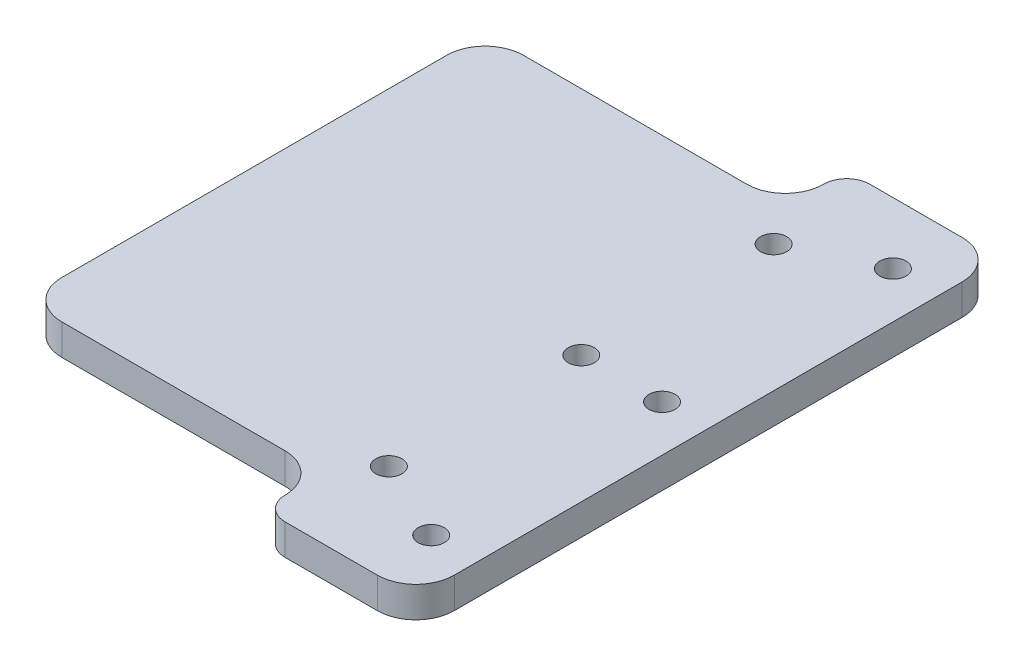
SolidWorks part; units mm, degrees
ref_plane "前视基准面" through (0, 0, 0) normal (0, 0, 1) x (1, 0, 0)
ref_plane "上视基准面" through (0, 0, 0) normal (0, 1, 0) x (1, 0, 0)
ref_plane "右视基准面" through (0, 0, 0) normal (1, 0, 0) x (0, 0, -1)
sketch "草图1" plane through (0, 0, 0) normal (0, 1, 0) x (1, 0, 0)
  line L0 (42.5, 25) -> (42.5, -25) construction
  line L5 (0, 0) -> (0, 30)
  line L6 (0, 30) -> (39, 30)
  line L7 (42.5, 0) -> (0, 0) construction
  line L8 (0, 0) -> (53, 0) construction
  line L9 (53, 30) -> (53, -30) construction
  line L10 (39, 30) -> (39, 38)
  line L11 (39, 38) -> (59, 38)
  line L12 (59, 38) -> (59, -38)
  line L13 (59, -38) -> (39, -38)
  line L14 (39, -38) -> (39, -30)
  line L15 (39, -30) -> (0, -30)
  line L16 (0, -30) -> (0, 0)
  circle A0 centre (42.5, 25) radius 1.7
  circle A1 centre (42.5, -25) radius 1.7
  circle A2 centre (42.5, 0) radius 1.7
  circle A3 centre (53, 30) radius 1.7
  circle A4 centre (53, 0) radius 1.7
  circle A5 centre (53, -30) radius 1.7
  point P0 (0, 0)
  dimension "D2" = 3.4
  dimension "D1" = 50
  dimension "D3" = 10.5
  dimension "D4" = 6
  dimension "D5" = 8
  dimension "D6" = 60
  dimension "D7" = 42.5
  dimension "D8" = 20
  dimension "D9" = 39
  dimension "D10" = 60
extrude "凸台-拉伸1" add sketch "草图1" along normal blind 4
sketch "草图2" plane through (0, 4, 0) normal (0, 1, 0) x (1, 0, 0)
  line L0 (-20.6269, -154.0352) -> (-20.6269, -168.0352) construction
  circle A1 centre (-20.6269, -168.0352) radius 1.5
  circle A2 centre (-20.6269, -168.0352) radius 1.5
  circle A3 centre (-17.1269, -171.5352) radius 1.5
  circle A4 centre (-17.1269, -171.5352) radius 1.5
  circle A5 centre (-10.1269, -164.5352) radius 1.5
  circle A6 centre (-10.1269, -164.5352) radius 1.5
  circle A7 centre (-10.1269, -178.5352) radius 1.5
  circle A8 centre (-10.1269, -178.5352) radius 1.5
  circle A9 centre (-3.1269, -171.5352) radius 1.5
  circle A10 centre (-3.1269, -171.5352) radius 1.5
  circle A11 centre (-44.6269, -171.5352) radius 2
  circle A13 centre (-44.6269, -161.5352) radius 2
  circle A15 centre (3.3731, -161.5352) radius 2
  circle A16 centre (3.3731, -161.5352) radius 2
  circle A17 centre (3.3731, -171.5352) radius 2
  circle A18 centre (3.3731, -171.5352) radius 2
  circle A19 centre (-20.6269, -154.0352) radius 1.5
  circle A20 centre (-20.6269, -154.0352) radius 1.5
  circle A21 centre (-13.6269, -161.0352) radius 1.5
  circle A22 centre (-13.6269, -161.0352) radius 1.5
  circle A23 centre (-31.1269, -178.5352) radius 1.5
  circle A24 centre (-38.1269, -171.5352) radius 1.5
  circle A25 centre (-24.1269, -171.5352) radius 1.5
  circle A28 centre (-31.1269, -164.5352) radius 1.5
  dimension "D1" = 0
  dimension "D2" = 0
  dimension "D3" = 0
  dimension "D4" = 0
  dimension "D5" = 0
  dimension "D8" = 0
  dimension "D9" = 0
  dimension "D10" = 0
  dimension "D11" = 0
extrude "切除-拉伸1" cut sketch "草图2" against normal through all contours A13 | A11 | A24 | A28 | A23 | A25 | A20 | A4 | A16 rebuild error yes
fillet "圆角1" radius 5 6 edges at (0, 2, 30) (0, 2, -30) (39, 2, -30) (39, 2, 30) (59, 2, 38) (59, 2, -38)
fillet "圆角2" radius 3 2 edges at (39, 2, 38) (39, 2, -38)
